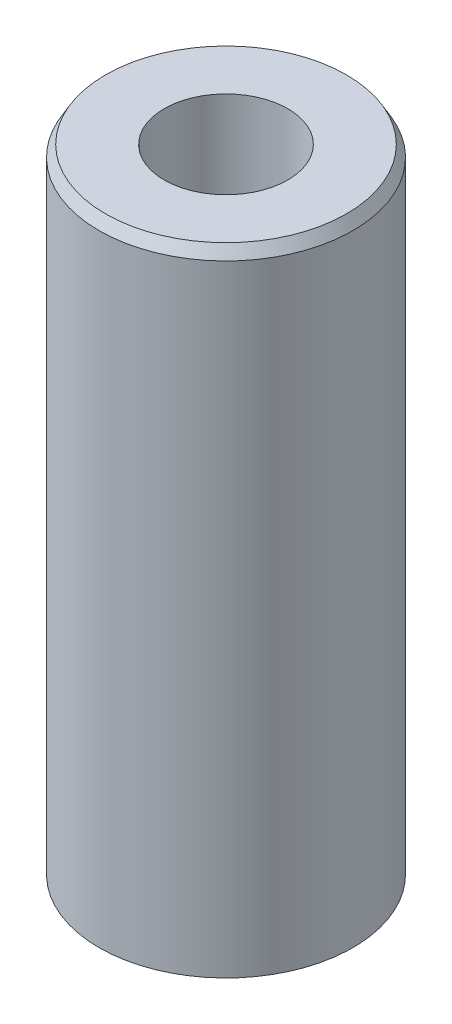
SolidWorks part; units mm, degrees
ref_plane "Front Plane" through (0, 0, 0) normal (0, 0, 1) x (1, 0, 0)
ref_plane "Top Plane" through (0, 0, 0) normal (0, 1, 0) x (1, 0, 0)
ref_plane "Right Plane" through (0, 0, 0) normal (1, 0, 0) x (0, 0, -1)
sketch "Sketch1" plane through (0, 0, 0) normal (0, 1, 0) x (1, 0, 0)
  circle A0 centre (0, 0) radius 20
  dimension "SHAFT_OD" = 40
extrude "Boss-Extrude1" add sketch "Sketch1" along normal blind 100.6309
sketch "Sketch2" plane through (0, 0, 0) normal (0, 1, 0) x (1, 0, 0)
  circle A0 centre (0, 0) radius 9.7364
  dimension "BORE_D" = 19.4728
extrude "Cut-Extrude1" cut sketch "Sketch2" along normal through all
chamfer "Chamfer1" distance 1.7751 angle 30 2 edges at (0, 100.6309, 20) (0, 0, 20) first distance on face at (0, 100.6309, 20) first distance on face at (0, 0, 9.7364)
